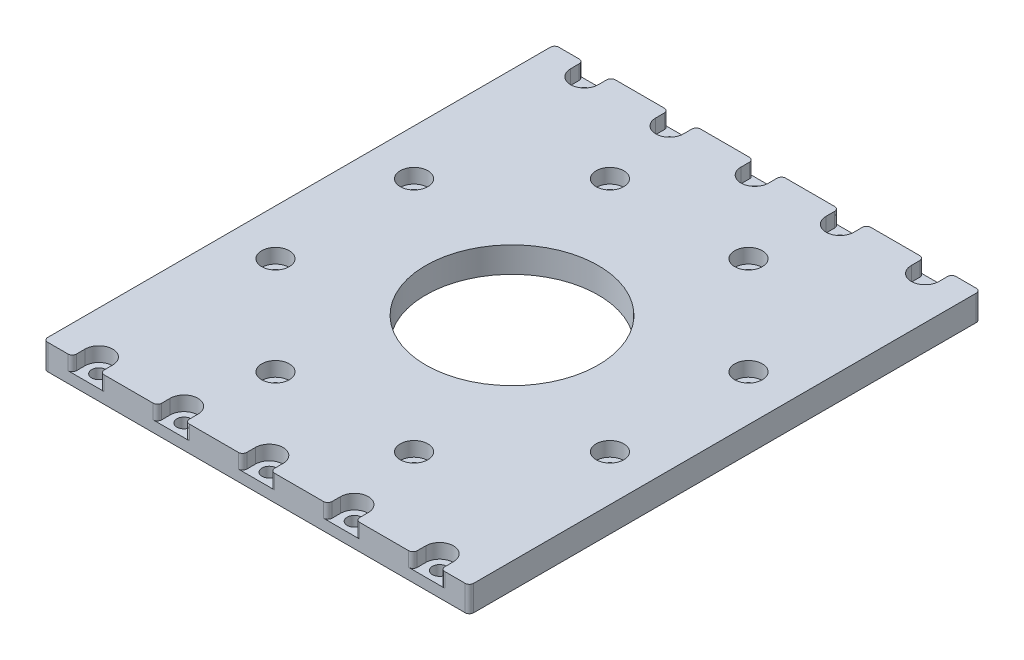
SolidWorks part; units mm, degrees
material "6061-T6 (SS)"
ref_plane "Front Plane" through (0, 0, 0) normal (0, 0, 1) x (1, 0, 0)
ref_plane "Top Plane" through (0, 0, 0) normal (0, 1, 0) x (1, 0, 0)
ref_plane "Right Plane" through (0, 0, 0) normal (1, 0, 0) x (0, 0, -1)
sketch "Sketch1" plane through (0, 0, 0) normal (0, 1, 0) x (1, 0, 0)
  circle A0 centre (0, 0) radius 50
  circle A1 centre (0, 0) radius 20.25
  dimension "D1" = 100
  dimension "D2" = 40.5
extrude "Boss-Extrude1" add sketch "Sketch1" along normal blind 6
sketch "Sketch2" plane through (0, 6, 0) normal (0, 1, 0) x (1, 0, 0)
  line L0 (-16.264, 39.2649) -> (16.264, 39.2649) construction
  circle A0 centre (0, 0) radius 42.5 construction
  point P4 (-16.264, 39.2649)
  point P10 (16.264, 39.2649)
  point P11 (39.2649, 16.264)
  point P12 (39.2649, -16.264)
  point P13 (16.264, -39.2649)
  point P14 (-16.264, -39.2649)
  point P15 (-39.2649, -16.264)
  point P16 (-39.2649, 16.264)
  dimension "D1" = 85
  dimension "D2" = 8
hole_wizard "CBORE for M3 Hex Socket Head Cap Screw2" positions "Sketch2" profile "Sketch3" counterbore size "M3" standard "DIN" end condition through all
sketch "Sketch3" plane through (-39.2649, 6, -16.264) normal (1, 0, 0) x (0, 0, 1)
  line L0 (0, 0) -> (0, 6)
  line L1 (0, 6) -> (1.7, 6)
  line L3 (1.7, 6) -> (1.7, 3.4)
  line L4 (1.7, 3.4) -> (3.25, 3.4)
  line L5 (3.25, 3.4) -> (3.25, 0)
  line L7 (3.25, 0) -> (0, 0)
  line L11 (0, -6.35) -> (0, 107.95) construction
  dimension "Thru Hole Dia." = 3.4
  dimension "Thru Hole Depth" = 6
  dimension "C'Bore Dia." = 6.5
  dimension "C'Bore Depth" = 3.4
sketch "Sketch6" plane through (0, 6, 0) normal (0, 1, 0) x (1, 0, 0)
  line L0 (-50, 0) -> (-50, -60)
  line L1 (-50, -60) -> (50, -60)
  line L2 (50, -60) -> (50, 0)
  circle A0 centre (0, 0) radius 50 construction
  arc A1 (-50, 0) -> (50, 0) centre (0, 0) ccw
  dimension "D1" = 60
extrude "Boss-Extrude2" add sketch "Sketch6" against normal up to surface (6 mm away) up to face at (-16.264, 0, -37.5649)
sketch "Sketch10" plane through (0, 6, 0) normal (0, 1, 0) x (1, 0, 0)
  line L0 (-50, 0) -> (-50, 60)
  line L1 (-50, 60) -> (50, 60)
  line L2 (50, 60) -> (50, 0)
  arc A0 (50, 0) -> (-50, 0) centre (0, 0) ccw construction
  arc A1 (50, 0) -> (-50, 0) centre (0, 0) ccw
  dimension "D1" = 60
extrude "Boss-Extrude3" add sketch "Sketch10" against normal up to surface (6 mm away) up to face at (-16.264, 0, -37.5649)
sketch "Sketch11" plane through (0, 6, 0) normal (0, 1, 0) x (1, 0, 0)
  line L0 (50, 60) -> (-50, 60) construction
  line L3 (0, 0) -> (0, 57) construction
  line L4 (0, 0) -> (-50000, 0) construction
  point P0 (-40, 57)
  point P13 (-20, 57)
  point P14 (0, 57)
  point P15 (20, 57)
  point P16 (40, 57)
  point P57 (40, -57)
  point P58 (20, -57)
  point P59 (0, -57)
  point P60 (-20, -57)
  point P61 (-40, -57)
  dimension "D1" = 3
  dimension "D2" = 5
  dimension "D5" = 20
hole_wizard "CBORE for M3 Hex Socket Head Cap Screw1" positions "Sketch11" profile "Sketch12" counterbore size "M3" standard "DIN" end condition through all
sketch "Sketch12" plane through (-40, 6, -57) normal (1, 0, 0) x (0, 0, 1)
  line L0 (0, 0) -> (0, 6)
  line L1 (0, 6) -> (1.7, 6)
  line L3 (1.7, 6) -> (1.7, 3.4)
  line L4 (1.7, 3.4) -> (3.25, 3.4)
  line L5 (3.25, 3.4) -> (3.25, 0)
  line L7 (3.25, 0) -> (0, 0)
  line L11 (0, -6.35) -> (0, 107.95) construction
  dimension "Thru Hole Dia." = 3.4
  dimension "Thru Hole Depth" = 6
  dimension "C'Bore Dia." = 6.5
  dimension "C'Bore Depth" = 3.4
sketch "Sketch13" plane through (0, 6, 0) normal (0, 1, 0) x (1, 0, 0)
  line L0 (-43.25, 57) -> (-43.25, 60)
  line L1 (-41.25, 60) -> (-50, 60) construction
  line L2 (-43.25, 60) -> (-36.75, 60)
  line L3 (-21.25, 60) -> (-38.75, 60) construction
  line L4 (-36.75, 60) -> (-36.75, 57)
  line L5 (-23.25, 57) -> (-23.25, 60)
  line L6 (-23.25, 60) -> (-16.75, 60)
  line L7 (-16.75, 60) -> (-16.75, 57)
  line L8 (-3.25, 57) -> (-3.25, 60)
  line L9 (-3.25, 60) -> (3.25, 60)
  line L10 (3.25, 60) -> (3.25, 57)
  line L11 (16.75, 57) -> (16.75, 60)
  line L12 (16.75, 60) -> (23.25, 60)
  line L13 (23.25, 60) -> (23.25, 57)
  line L14 (36.75, 57) -> (36.75, 60)
  line L15 (36.75, 60) -> (43.25, 60)
  line L16 (43.25, 60) -> (43.25, 57)
  line L17 (0, 0) -> (69.1463, 0) construction
  line L18 (43.25, -60) -> (43.25, -57)
  line L19 (36.75, -60) -> (43.25, -60)
  line L20 (36.75, -57) -> (36.75, -60)
  line L21 (23.25, -60) -> (23.25, -57)
  line L22 (16.75, -60) -> (23.25, -60)
  line L23 (16.75, -57) -> (16.75, -60)
  line L24 (3.25, -60) -> (3.25, -57)
  line L25 (-3.25, -60) -> (3.25, -60)
  line L26 (-3.25, -57) -> (-3.25, -60)
  line L27 (-16.75, -60) -> (-16.75, -57)
  line L28 (-23.25, -60) -> (-16.75, -60)
  line L29 (-23.25, -57) -> (-23.25, -60)
  line L30 (-36.75, -60) -> (-36.75, -57)
  line L31 (-43.25, -60) -> (-36.75, -60)
  line L32 (-43.25, -57) -> (-43.25, -60)
  arc A0 (-41.25, 60) -> (-38.75, 60) centre (-40, 57) ccw construction
  arc A1 (-43.25, 57) -> (-36.75, 57) centre (-40, 57) ccw
  arc A2 (-23.25, 57) -> (-16.75, 57) centre (-20, 57) ccw
  arc A3 (-3.25, 57) -> (3.25, 57) centre (0, 57) ccw
  arc A4 (16.75, 57) -> (23.25, 57) centre (20, 57) ccw
  arc A5 (36.75, 57) -> (43.25, 57) centre (40, 57) ccw
  arc A6 (36.75, -57) -> (43.25, -57) centre (40, -57) cw
  arc A7 (16.75, -57) -> (23.25, -57) centre (20, -57) cw
  arc A8 (-3.25, -57) -> (3.25, -57) centre (0, -57) cw
  arc A9 (-23.25, -57) -> (-16.75, -57) centre (-20, -57) cw
  arc A10 (-43.25, -57) -> (-36.75, -57) centre (-40, -57) cw
  dimension "D1" = 5
extrude "Cut-Extrude1" cut sketch "Sketch13" against normal up to surface (3.4 mm away) up to face at (-40, 2.6, -56.875)
fillet "Fillet1" radius 1 24 edges at (-43.25, 4.3, 60) (-50, 3, 60) (-50, 3, -60) (-36.75, 4.3, -60) (-23.25, 4.3, -60) (-16.75, 4.3, -60) (-3.25, 4.3, -60) (3.25, 4.3, -60) (16.75, 4.3, -60) (23.25, 4.3, -60) (36.75, 4.3, -60) (43.25, 4.3, -60) (50, 3, -60) (50, 3, 60) (43.25, 4.3, 60) (36.75, 4.3, 60) (23.25, 4.3, 60) (16.75, 4.3, 60) (3.25, 4.3, 60) (-3.25, 4.3, 60) (-16.75, 4.3, 60) (-23.25, 4.3, 60) (-36.75, 4.3, 60) (-43.25, 4.3, -60)
